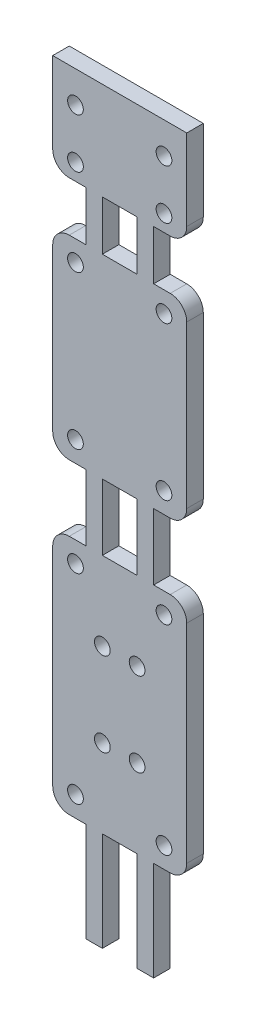
SolidWorks part; units mm, degrees
ref_plane "Front Plane" through (0, 0, 0) normal (0, 0, 1) x (1, 0, 0)
ref_plane "Top Plane" through (0, 0, 0) normal (0, 1, 0) x (1, 0, 0)
ref_plane "Right Plane" through (0, 0, 0) normal (1, 0, 0) x (0, 0, -1)
sketch "Sketch1" plane through (0, 0, 0) normal (0, 0, 1) x (1, 0, 0)
  line L0 (4, 26) -> (2, 26)
  line L1 (0, 1.5) -> (16.2, 1.5) construction
  line L2 (0, 14) -> (4, 14) construction
  line L3 (0, 14) -> (0, 1.5) construction
  line L4 (6, 14) -> (6, 26)
  line L5 (4, 14) -> (4, 26)
  line L6 (0, 28) -> (0, 53.14)
  line L7 (0, 94.665) -> (0, 104.46)
  line L8 (6, 14) -> (10.2, 14) construction
  line L9 (8.1, 1.5) -> (8.1, 104.46) construction
  line L10 (0, 104.46) -> (16.2, 104.46)
  line L11 (6, 63.14) -> (10.2, 63.14)
  line L12 (6, 55.14) -> (10.2, 55.14)
  line L13 (6, 92.665) -> (10.2, 92.665)
  line L14 (6, 86.665) -> (10.2, 86.665)
  line L15 (16.2, 84.665) -> (16.2, 65.14)
  line L16 (10.2, 86.665) -> (10.2, 92.665)
  line L17 (14.2, 55.14) -> (12.2, 55.14)
  line L18 (2, 92.665) -> (4, 92.665)
  line L19 (2, 86.665) -> (4, 86.665)
  line L20 (2, 63.14) -> (4, 63.14)
  line L21 (10.2, 55.14) -> (10.2, 63.14)
  line L22 (4, 86.665) -> (4, 92.665)
  line L23 (4, 55.14) -> (4, 63.14)
  line L24 (6, 55.14) -> (6, 63.14)
  line L25 (2, 55.14) -> (4, 55.14)
  line L26 (6, 86.665) -> (6, 92.665)
  line L27 (12.2, 55.14) -> (12.2, 63.14)
  line L28 (12.2, 86.665) -> (12.2, 92.665)
  line L29 (14.2, 63.14) -> (12.2, 63.14)
  line L30 (14.2, 86.665) -> (12.2, 86.665)
  line L31 (14.2, 92.665) -> (12.2, 92.665)
  line L32 (6, 26) -> (10.2, 26)
  line L33 (4, 14) -> (6, 14)
  line L34 (16.2, 94.665) -> (16.2, 104.46)
  line L35 (16.2, 28) -> (16.2, 53.14)
  line L36 (12.2, 14) -> (12.2, 26)
  line L37 (10.2, 14) -> (10.2, 26)
  line L38 (16.2, 14) -> (16.2, 1.5) construction
  line L39 (16.2, 14) -> (12.2, 14) construction
  line L40 (12.2, 26) -> (14.2, 26)
  line L41 (10.2, 14) -> (12.2, 14)
  line L58 (0, 84.665) -> (0, 65.14)
  circle A0 centre (2.85, 11.5) radius 0.95 construction
  circle A1 centre (13.45, 94.665) radius 0.95
  circle A2 centre (13.45, 84.165) radius 0.95
  circle A3 centre (2.85, 5.5) radius 0.95 construction
  circle A4 centre (13.45, 65.64) radius 0.95
  circle A5 centre (13.45, 52.64) radius 0.95
  circle A6 centre (13.45, 28.5) radius 0.95
  circle A7 centre (10.2, 35.5) radius 0.95
  arc A8 (16.2, 28) -> (14.2, 26) centre (14.2, 28) cw
  circle A9 centre (10.2, 45.64) radius 0.95
  arc A10 (2, 86.665) -> (0, 84.665) centre (2, 84.665) ccw
  arc A11 (14.2, 55.14) -> (16.2, 53.14) centre (14.2, 53.14) cw
  circle A12 centre (13.45, 100.665) radius 0.95
  arc A13 (16.2, 94.665) -> (14.2, 92.665) centre (14.2, 94.665) cw
  arc A14 (16.2, 65.14) -> (14.2, 63.14) centre (14.2, 65.14) cw
  arc A15 (0, 65.14) -> (2, 63.14) centre (2, 65.14) ccw
  arc A16 (0, 94.665) -> (2, 92.665) centre (2, 94.665) ccw
  arc A17 (14.2, 86.665) -> (16.2, 84.665) centre (14.2, 84.665) cw
  circle A18 centre (2.75, 100.665) radius 0.95
  circle A19 centre (13.35, 5.5) radius 0.95 construction
  circle A20 centre (13.35, 11.5) radius 0.95 construction
  arc A22 (2, 55.14) -> (0, 53.14) centre (2, 53.14) ccw
  circle A24 centre (6, 45.64) radius 0.95
  arc A26 (0, 28) -> (2, 26) centre (2, 28) ccw
  circle A30 centre (6, 35.5) radius 0.95
  circle A32 centre (2.75, 28.5) radius 0.95
  circle A34 centre (2.75, 52.64) radius 0.95
  circle A36 centre (2.75, 65.64) radius 0.95
  circle A38 centre (2.75, 84.165) radius 0.95
  circle A40 centre (2.75, 94.665) radius 0.95
  point P9 (8.1, 92.665)
  point P11 (8.1, 86.665)
  point P16 (8.1, 63.14)
  point P17 (8.1, 55.14)
  point P20 (8.1, 63.14)
  point P21 (8.1, 55.14)
  point P58 (8.1, 26)
  point P66 (8.1, 14)
  point P83 (8.1, 26)
  point P96 (8.1, 92.665)
  point P100 (8.1, 14)
  dimension "D8" = 2
  dimension "D28" = 2
  dimension "D30" = 2
  dimension "D32" = 2
  dimension "D42" = 1.9
  dimension "D44" = 2
  dimension "D2" = 2.85
  dimension "D3" = 4
  dimension "D4" = 2.85
  dimension "D5" = 6
  dimension "D6" = 2.5
  dimension "D7" = 12
  dimension "D9" = 2.5
  dimension "D10" = 9.5
  dimension "D11" = 2.75
  dimension "D13" = 2.5
  dimension "D14" = 9.5
  dimension "D15" = 2.75
  dimension "D17" = 29.14
  dimension "D12" = 6
  dimension "D16" = 6
  dimension "D18" = 2.75
  dimension "D19" = 2.5
  dimension "D20" = 8
  dimension "D21" = 2
  dimension "D22" = 2
  dimension "D23" = 2
  dimension "D24" = 2
  dimension "D25" = 2.75
  dimension "D26" = 2.5
  dimension "D27" = 23.525
  dimension "D39" = 2
  dimension "D40" = 2.75
  dimension "D41" = 6
  dimension "D45" = 2.75
  dimension "D46" = 6
  dimension "D47" = 11.795
  dimension "D48" = 8.1
  dimension "D49" = 2
extrude "Boss-Extrude1" add sketch "Sketch1" along normal blind 2
sketch "Sketch2" plane through (0, 0, 2) normal (0, 0, 1) x (1, 0, 0)
  line L0 (4, 92.665) -> (12.2, 92.665)
  line L1 (12.2, 92.665) -> (12.2, 86.665)
  line L2 (12.2, 86.665) -> (4, 86.665)
  line L3 (4, 86.665) -> (4, 92.665)
  line L4 (4, 63.14) -> (12.2, 63.14)
  line L5 (12.2, 63.14) -> (12.2, 55.14)
  line L6 (12.2, 55.14) -> (4, 55.14)
  line L7 (4, 55.14) -> (4, 63.14)
  line L8 (4, 26) -> (12.2, 26)
  line L9 (12.2, 26) -> (12.2, 14)
  line L10 (12.2, 14) -> (4, 14)
  line L11 (4, 14) -> (4, 26)
extrude "Cut-Extrude1" [suppressed] cut sketch "Sketch2" against normal up to surface (2 mm away) up to face at (3.7, 94.665, 0)
equation "\"D48@Sketch1\"= ( \"fingerWidth@parametersSketch@prostheticParameters.SLDPRT\" ) / 2 'Ring Width"
equation "\"D17@Sketch1\"= \"HL@parametersSketch@prostheticParameters.SLDPRT\" * 0.244 - 4 - 12'Ring PIP Length"
equation "\"D27@Sketch1\"= \"HL@parametersSketch@prostheticParameters.SLDPRT\" * 0.165 - 3 - 4'Ring MIP Length"
equation "\"D47@Sketch1\"= \"HL@parametersSketch@prostheticParameters.SLDPRT\" * 0.107 - 3 - 5'Ring DIP Length - Gap fingertip"
equation "\"D42@Sketch1\"= 1.5 + \"tol1@parametersSketch@prostheticParameters.SLDPRT\""
